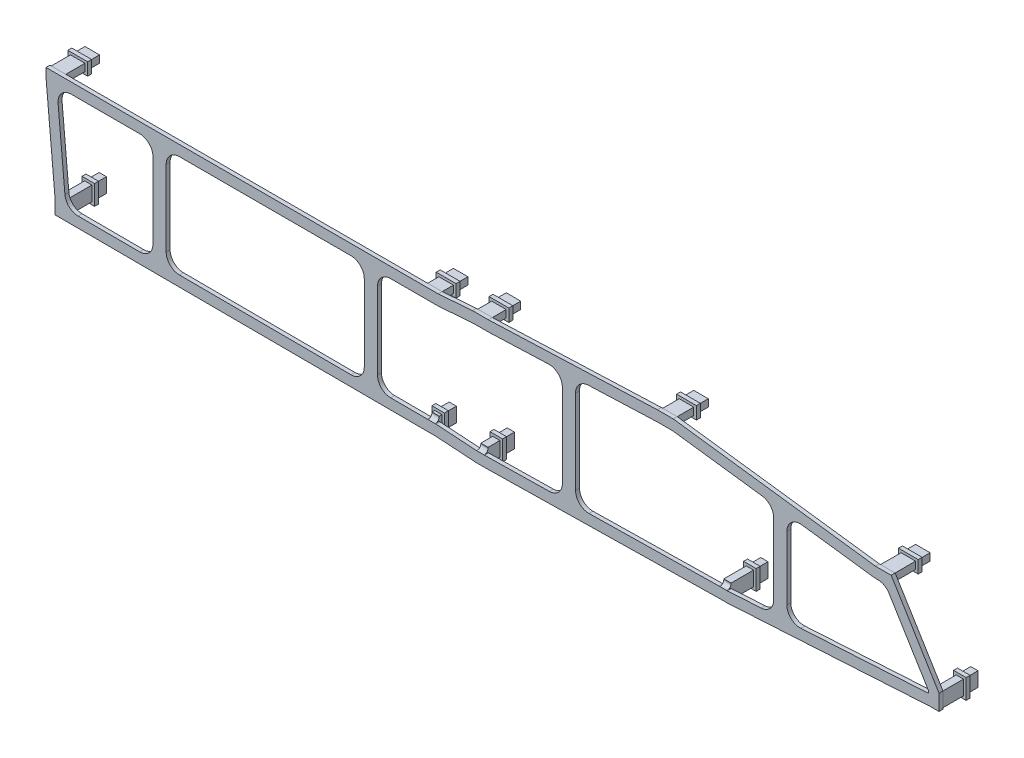
SolidWorks part; units mm, degrees
ref_plane "Front Plane" through (0, 0, 0) normal (0, 0, 1) x (1, 0, 0)
ref_plane "Top Plane" through (0, 0, 0) normal (0, 1, 0) x (1, 0, 0)
ref_plane "Right Plane" through (0, 0, 0) normal (1, 0, 0) x (0, 0, -1)
ref_plane "Plane11" through (0, 0, 7) normal (0, 0, 1) x (1, 0, 0)
ref_plane "Plane12" through (0, 0, 12) normal (0, 0, 1) x (1, 0, 0)
sketch "Sketch13" plane through (0, 0, 12) normal (0, 0, 1) x (1, 0, 0)
  line L0 (-277.75, -90) -> (-284.25, -90)
  line L1 (-284.25, -90) -> (-284.25, -78)
  line L2 (-284.25, -78) -> (-291, -3.25)
  line L3 (-291, -3.25) -> (-291, 3.25)
  line L4 (-291, 3.25) -> (-279, 3.25)
  line L5 (-279, 3.25) -> (-6, 3.25)
  line L6 (-6, 3.25) -> (6, 3.25)
  line L7 (6, 3.25) -> (32, 5.25)
  line L8 (32, 5.25) -> (44, 5.25)
  line L9 (44, 5.25) -> (172, 10.25)
  line L10 (172, 10.25) -> (184, 10.25)
  line L11 (184, 10.25) -> (337, -9.75)
  line L12 (337, -9.75) -> (349, -9.75)
  line L13 (349, -9.75) -> (385.25, -69)
  line L14 (385.25, -69) -> (385.25, -81)
  line L15 (385.25, -81) -> (378.75, -81)
  line L16 (378.75, -81) -> (225.25, -90)
  line L17 (225.25, -90) -> (218.75, -90)
  line L18 (218.75, -90) -> (41.25, -93)
  line L19 (41.25, -93) -> (34.75, -93)
  line L20 (34.75, -93) -> (4.25, -91)
  line L21 (4.25, -91) -> (-2.25, -91)
  line L22 (-2.25, -91) -> (-277.75, -90)
extrude "STUD LINK" add sketch "Sketch13" along normal blind 3
ref_plane "Plane1" through (0, 0, 0) normal (0, 0, 1) x (1, 0, 0)
ref_plane "Plane2" through (0, 0, -2) normal (0, 0, 1) x (1, 0, 0)
ref_plane "Plane3" through (0, 0, -4) normal (0, 0, 1) x (1, 0, 0)
ref_plane "Plane4" through (0, 0, 7) normal (0, 0, 1) x (1, 0, 0)
ref_plane "Plane5" through (0, 0, 0) normal (0, 0, 1) x (1, 0, 0)
ref_plane "Plane6" through (0, 0, -8) normal (0, 0, 1) x (1, 0, 0)
ref_plane "Plane7" through (0, 0, -7) normal (0, 0, 1) x (1, 0, 0)
ref_plane "Plane8" through (0, 0, -7) normal (0, 0, 1) x (1, 0, 0)
ref_plane "Plane9" through (0, 0, -6) normal (0, 0, 1) x (1, 0, 0)
ref_plane "Plane10" through (0, 0, -10) normal (0, 0, 1) x (1, 0, 0)
sketch "Sketch1" plane through (0, 0, 0) normal (0, 0, 1) x (1, 0, 0)
  line L8 (-5.5, 2.75) -> (-5.5, -2.75)
  line L9 (-5.5, -2.75) -> (5.5, -2.75)
  line L10 (5.5, -2.75) -> (5.5, 2.75)
  line L11 (5.5, 2.75) -> (-5.5, 2.75)
  line L12 (-5.5, 2.75) -> (-5.5, -2.75)
  line L13 (-5.5, -2.75) -> (5.5, -2.75)
  line L14 (5.5, -2.75) -> (5.5, 2.75)
  line L15 (5.5, 2.75) -> (-5.5, 2.75)
  dimension "D1" = 0.5
extrude "Boss-Extrude1" add sketch "Sketch1" against normal blind 8 and the other way up to next
sketch "Sketch2" plane through (0, 0, -2) normal (0, 0, 1) x (1, 0, 0)
  line L8 (43.5, 4.75) -> (32.5, 4.75)
  line L9 (43.5, -0.75) -> (43.5, 4.75)
  line L10 (32.5, -0.75) -> (43.5, -0.75)
  line L11 (32.5, 4.75) -> (32.5, -0.75)
  line L12 (43.5, 4.75) -> (32.5, 4.75)
  line L13 (43.5, -0.75) -> (43.5, 4.75)
  line L14 (32.5, -0.75) -> (43.5, -0.75)
  line L15 (32.5, 4.75) -> (32.5, -0.75)
  dimension "D1" = 0.5
extrude "Boss-Extrude2" add sketch "Sketch2" against normal blind 8 and the other way up to next separate body
sketch "Sketch3" plane through (0, 0, -4) normal (0, 0, 1) x (1, 0, 0)
  line L8 (183.5, 9.75) -> (172.5, 9.75)
  line L9 (183.5, 4.25) -> (183.5, 9.75)
  line L10 (172.5, 4.25) -> (183.5, 4.25)
  line L11 (172.5, 9.75) -> (172.5, 4.25)
  line L12 (183.5, 9.75) -> (172.5, 9.75)
  line L13 (183.5, 4.25) -> (183.5, 9.75)
  line L14 (172.5, 4.25) -> (183.5, 4.25)
  line L15 (172.5, 9.75) -> (172.5, 4.25)
  dimension "D1" = 0.5
extrude "Boss-Extrude3" add sketch "Sketch3" against normal blind 8 and the other way up to next separate body
sketch "Sketch4" plane through (0, 0, 7) normal (0, 0, 1) x (1, 0, 0)
  line L8 (3.75, -79.5) -> (-1.75, -79.5)
  line L9 (3.75, -90.5) -> (3.75, -79.5)
  line L10 (-1.75, -90.5) -> (3.75, -90.5)
  line L11 (-1.75, -79.5) -> (-1.75, -90.5)
  line L12 (3.75, -79.5) -> (-1.75, -79.5)
  line L13 (3.75, -90.5) -> (3.75, -79.5)
  line L14 (-1.75, -90.5) -> (3.75, -90.5)
  line L15 (-1.75, -79.5) -> (-1.75, -90.5)
  dimension "D1" = 0.5
extrude "Boss-Extrude4" add sketch "Sketch4" against normal blind 8 and the other way up to next separate body
sketch "Sketch5" plane through (0, 0, 0) normal (0, 0, 1) x (1, 0, 0)
  line L8 (40.75, -81.5) -> (35.25, -81.5)
  line L9 (40.75, -92.5) -> (40.75, -81.5)
  line L10 (35.25, -92.5) -> (40.75, -92.5)
  line L11 (35.25, -81.5) -> (35.25, -92.5)
  line L12 (40.75, -81.5) -> (35.25, -81.5)
  line L13 (40.75, -92.5) -> (40.75, -81.5)
  line L14 (35.25, -92.5) -> (40.75, -92.5)
  line L15 (35.25, -81.5) -> (35.25, -92.5)
  dimension "D1" = 0.5
extrude "Boss-Extrude5" add sketch "Sketch5" against normal blind 8 and the other way up to next separate body
sketch "Sketch6" plane through (0, 0, -8) normal (0, 0, 1) x (1, 0, 0)
  line L8 (224.75, -78.5) -> (219.25, -78.5)
  line L9 (219.25, -78.5) -> (219.25, -89.5)
  line L10 (219.25, -89.5) -> (224.75, -89.5)
  line L11 (224.75, -89.5) -> (224.75, -78.5)
  line L12 (224.75, -78.5) -> (219.25, -78.5)
  line L13 (219.25, -78.5) -> (219.25, -89.5)
  line L14 (219.25, -89.5) -> (224.75, -89.5)
  line L15 (224.75, -89.5) -> (224.75, -78.5)
  dimension "D1" = 0.5
extrude "Boss-Extrude6" add sketch "Sketch6" against normal blind 8 and the other way up to next separate body
sketch "Sketch7" plane through (0, 0, -7) normal (0, 0, 1) x (1, 0, 0)
  line L8 (348.5, -10.25) -> (337.5, -10.25)
  line L9 (348.5, -15.75) -> (348.5, -10.25)
  line L10 (337.5, -15.75) -> (348.5, -15.75)
  line L11 (337.5, -10.25) -> (337.5, -15.75)
  line L12 (348.5, -10.25) -> (337.5, -10.25)
  line L13 (348.5, -15.75) -> (348.5, -10.25)
  line L14 (337.5, -15.75) -> (348.5, -15.75)
  line L15 (337.5, -10.25) -> (337.5, -15.75)
  dimension "D1" = 0.5
extrude "Boss-Extrude7" add sketch "Sketch7" against normal blind 8 and the other way up to next separate body
sketch "Sketch8" plane through (0, 0, -7) normal (0, 0, 1) x (1, 0, 0)
  line L8 (384.75, -69.5) -> (379.25, -69.5)
  line L9 (384.75, -80.5) -> (384.75, -69.5)
  line L10 (379.25, -80.5) -> (384.75, -80.5)
  line L11 (379.25, -69.5) -> (379.25, -80.5)
  line L12 (384.75, -69.5) -> (379.25, -69.5)
  line L13 (384.75, -80.5) -> (384.75, -69.5)
  line L14 (379.25, -80.5) -> (384.75, -80.5)
  line L15 (379.25, -69.5) -> (379.25, -80.5)
  dimension "D1" = 0.5
extrude "Boss-Extrude8" add sketch "Sketch8" against normal blind 8 and the other way up to next separate body
sketch "Sketch9" plane through (0, 0, -6) normal (0, 0, 1) x (1, 0, 0)
  line L8 (-279.5, 2.75) -> (-290.5, 2.75)
  line L9 (-279.5, -2.75) -> (-279.5, 2.75)
  line L10 (-290.5, -2.75) -> (-279.5, -2.75)
  line L11 (-290.5, 2.75) -> (-290.5, -2.75)
  line L12 (-279.5, 2.75) -> (-290.5, 2.75)
  line L13 (-279.5, -2.75) -> (-279.5, 2.75)
  line L14 (-290.5, -2.75) -> (-279.5, -2.75)
  line L15 (-290.5, 2.75) -> (-290.5, -2.75)
  dimension "D1" = 0.5
extrude "Boss-Extrude9" add sketch "Sketch9" against normal blind 8 and the other way up to next separate body
sketch "Sketch10" plane through (0, 0, -10) normal (0, 0, 1) x (1, 0, 0)
  line L8 (-278.25, -78.5) -> (-283.75, -78.5)
  line L9 (-278.25, -89.5) -> (-278.25, -78.5)
  line L10 (-283.75, -89.5) -> (-278.25, -89.5)
  line L11 (-283.75, -78.5) -> (-283.75, -89.5)
  line L12 (-278.25, -78.5) -> (-283.75, -78.5)
  line L13 (-278.25, -89.5) -> (-278.25, -78.5)
  line L14 (-283.75, -89.5) -> (-278.25, -89.5)
  line L15 (-283.75, -78.5) -> (-283.75, -89.5)
  dimension "D1" = 0.5
extrude "Boss-Extrude10" add sketch "Sketch10" against normal blind 8 and the other way up to next (22 mm away) separate body
sketch "Sketch14" plane through (0, 0, 0) normal (0, 0, 1) x (1, 0, 0)
  line L8 (-7.5, -4.75) -> (7.5, -4.75)
  line L9 (7.5, -4.75) -> (7.5, 4.75)
  line L10 (7.5, 4.75) -> (-7.5, 4.75)
  line L11 (-7.5, 4.75) -> (-7.5, -4.75)
  line L12 (-7.5, -4.75) -> (7.5, -4.75)
  line L13 (7.5, -4.75) -> (7.5, 4.75)
  line L14 (7.5, 4.75) -> (-7.5, 4.75)
  line L15 (-7.5, 4.75) -> (-7.5, -4.75)
  dimension "D1" = 1.5
extrude "Boss-Extrude14" add sketch "Sketch14" along normal blind 3
sketch "Sketch15" plane through (0, 0, -2) normal (0, 0, 1) x (1, 0, 0)
  line L8 (45.5, 6.75) -> (30.5, 6.75)
  line L9 (30.5, 6.75) -> (30.5, -2.75)
  line L10 (30.5, -2.75) -> (45.5, -2.75)
  line L11 (45.5, -2.75) -> (45.5, 6.75)
  line L12 (45.5, 6.75) -> (30.5, 6.75)
  line L13 (30.5, 6.75) -> (30.5, -2.75)
  line L14 (30.5, -2.75) -> (45.5, -2.75)
  line L15 (45.5, -2.75) -> (45.5, 6.75)
  dimension "D1" = 1.5
extrude "Boss-Extrude15" add sketch "Sketch15" along normal blind 3
sketch "Sketch16" plane through (0, 0, -4) normal (0, 0, 1) x (1, 0, 0)
  line L8 (185.5, 11.75) -> (170.5, 11.75)
  line L9 (170.5, 11.75) -> (170.5, 2.25)
  line L10 (170.5, 2.25) -> (185.5, 2.25)
  line L11 (185.5, 2.25) -> (185.5, 11.75)
  line L12 (185.5, 11.75) -> (170.5, 11.75)
  line L13 (170.5, 11.75) -> (170.5, 2.25)
  line L14 (170.5, 2.25) -> (185.5, 2.25)
  line L15 (185.5, 2.25) -> (185.5, 11.75)
  dimension "D1" = 1.5
extrude "Boss-Extrude16" add sketch "Sketch16" along normal blind 3
sketch "Sketch17" plane through (0, 0, 7) normal (0, 0, 1) x (1, 0, 0)
  line L8 (5.75, -77.5) -> (-3.75, -77.5)
  line L9 (-3.75, -77.5) -> (-3.75, -92.5)
  line L10 (-3.75, -92.5) -> (5.75, -92.5)
  line L11 (5.75, -92.5) -> (5.75, -77.5)
  line L12 (5.75, -77.5) -> (-3.75, -77.5)
  line L13 (-3.75, -77.5) -> (-3.75, -92.5)
  line L14 (-3.75, -92.5) -> (5.75, -92.5)
  line L15 (5.75, -92.5) -> (5.75, -77.5)
  dimension "D1" = 1.5
extrude "Boss-Extrude17" add sketch "Sketch17" along normal blind 3
sketch "Sketch18" plane through (0, 0, 0) normal (0, 0, 1) x (1, 0, 0)
  line L8 (42.75, -79.5) -> (33.25, -79.5)
  line L9 (42.75, -94.5) -> (42.75, -79.5)
  line L10 (33.25, -94.5) -> (42.75, -94.5)
  line L11 (33.25, -79.5) -> (33.25, -94.5)
  line L12 (42.75, -79.5) -> (33.25, -79.5)
  line L13 (42.75, -94.5) -> (42.75, -79.5)
  line L14 (33.25, -94.5) -> (42.75, -94.5)
  line L15 (33.25, -79.5) -> (33.25, -94.5)
  dimension "D1" = 1.5
extrude "Boss-Extrude18" add sketch "Sketch18" along normal blind 3
sketch "Sketch19" plane through (0, 0, -8) normal (0, 0, 1) x (1, 0, 0)
  line L8 (226.75, -76.5) -> (217.25, -76.5)
  line L9 (226.75, -91.5) -> (226.75, -76.5)
  line L10 (217.25, -91.5) -> (226.75, -91.5)
  line L11 (217.25, -76.5) -> (217.25, -91.5)
  line L12 (226.75, -76.5) -> (217.25, -76.5)
  line L13 (226.75, -91.5) -> (226.75, -76.5)
  line L14 (217.25, -91.5) -> (226.75, -91.5)
  line L15 (217.25, -76.5) -> (217.25, -91.5)
  dimension "D1" = 1.5
extrude "Boss-Extrude19" add sketch "Sketch19" along normal blind 3
sketch "Sketch20" plane through (0, 0, -7) normal (0, 0, 1) x (1, 0, 0)
  line L8 (350.5, -8.25) -> (335.5, -8.25)
  line L9 (335.5, -8.25) -> (335.5, -17.75)
  line L10 (335.5, -17.75) -> (350.5, -17.75)
  line L11 (350.5, -17.75) -> (350.5, -8.25)
  line L12 (350.5, -8.25) -> (335.5, -8.25)
  line L13 (335.5, -8.25) -> (335.5, -17.75)
  line L14 (335.5, -17.75) -> (350.5, -17.75)
  line L15 (350.5, -17.75) -> (350.5, -8.25)
  dimension "D1" = 1.5
extrude "Boss-Extrude20" add sketch "Sketch20" along normal blind 3
sketch "Sketch21" plane through (0, 0, -7) normal (0, 0, 1) x (1, 0, 0)
  line L8 (386.75, -67.5) -> (377.25, -67.5)
  line L9 (386.75, -82.5) -> (386.75, -67.5)
  line L10 (377.25, -82.5) -> (386.75, -82.5)
  line L11 (377.25, -67.5) -> (377.25, -82.5)
  line L12 (386.75, -67.5) -> (377.25, -67.5)
  line L13 (386.75, -82.5) -> (386.75, -67.5)
  line L14 (377.25, -82.5) -> (386.75, -82.5)
  line L15 (377.25, -67.5) -> (377.25, -82.5)
  dimension "D1" = 1.5
extrude "Boss-Extrude21" add sketch "Sketch21" along normal blind 3
sketch "Sketch22" plane through (0, 0, -6) normal (0, 0, 1) x (1, 0, 0)
  line L8 (-277.5, 4.75) -> (-292.5, 4.75)
  line L9 (-277.5, -4.75) -> (-277.5, 4.75)
  line L10 (-292.5, -4.75) -> (-277.5, -4.75)
  line L11 (-292.5, 4.75) -> (-292.5, -4.75)
  line L12 (-277.5, 4.75) -> (-292.5, 4.75)
  line L13 (-277.5, -4.75) -> (-277.5, 4.75)
  line L14 (-292.5, -4.75) -> (-277.5, -4.75)
  line L15 (-292.5, 4.75) -> (-292.5, -4.75)
  dimension "D1" = 1.5
extrude "Boss-Extrude22" add sketch "Sketch22" along normal blind 3
sketch "Sketch23" plane through (0, 0, -10) normal (0, 0, 1) x (1, 0, 0)
  line L15 (-276.25, -76.5) -> (-285.75, -76.5)
  line L16 (-285.75, -76.5) -> (-285.75, -91.5)
  line L17 (-276.25, -91.5) -> (-276.25, -76.5)
  line L18 (-285.75, -91.5) -> (-276.25, -91.5)
  line L19 (-276.25, -76.5) -> (-285.75, -76.5)
  line L20 (-285.75, -76.5) -> (-285.75, -91.5)
  line L21 (-276.25, -91.5) -> (-276.25, -76.5)
  line L22 (-285.75, -91.5) -> (-276.25, -91.5)
  dimension "D1" = 1.5
extrude "Boss-Extrude23" add sketch "Sketch23" along normal blind 3
sketch "Sketch24" plane through (0, 0, 15) normal (0, 0, 1) x (1, 0, 0)
  line L42 (-276.25, -82.0054) -> (-2.2355, -83)
  line L43 (-2.2355, -83) -> (4.512, -83)
  line L44 (4.512, -83) -> (35.012, -85)
  line L45 (35.012, -85) -> (41.1824, -85)
  line L46 (41.1824, -85) -> (218.6824, -82)
  line L47 (218.6824, -82) -> (225.0157, -82)
  line L48 (225.0157, -82) -> (377.25, -73.0742)
  line L49 (377.25, -73.0742) -> (377.25, -71.2531)
  line L50 (377.25, -71.2531) -> (344.516, -17.75)
  line L51 (344.516, -17.75) -> (336.4793, -17.75)
  line L52 (336.4793, -17.75) -> (183.4793, 2.25)
  line L53 (183.4793, 2.25) -> (172.1562, 2.25)
  line L54 (172.1562, 2.25) -> (44.1562, -2.75)
  line L55 (44.1562, -2.75) -> (32.3072, -2.75)
  line L56 (32.3072, -2.75) -> (6.3072, -4.75)
  line L57 (6.3072, -4.75) -> (-282.832, -4.75)
  line L58 (-282.832, -4.75) -> (-276.25, -77.6395)
  line L59 (-276.25, -77.6395) -> (-276.25, -82.0054)
  line L60 (-276.25, -82.0054) -> (-2.2355, -83)
  line L61 (-2.2355, -83) -> (4.512, -83)
  line L62 (4.512, -83) -> (35.012, -85)
  line L63 (35.012, -85) -> (41.1824, -85)
  line L64 (41.1824, -85) -> (218.6824, -82)
  line L65 (218.6824, -82) -> (225.0157, -82)
  line L66 (225.0157, -82) -> (377.25, -73.0742)
  line L67 (377.25, -73.0742) -> (377.25, -71.2531)
  line L68 (377.25, -71.2531) -> (344.516, -17.75)
  line L69 (344.516, -17.75) -> (336.4793, -17.75)
  line L70 (336.4793, -17.75) -> (183.4793, 2.25)
  line L71 (183.4793, 2.25) -> (172.1562, 2.25)
  line L72 (172.1562, 2.25) -> (44.1562, -2.75)
  line L73 (44.1562, -2.75) -> (32.3072, -2.75)
  line L74 (32.3072, -2.75) -> (6.3072, -4.75)
  line L75 (6.3072, -4.75) -> (-282.832, -4.75)
  line L76 (-282.832, -4.75) -> (-276.25, -77.6395)
  line L77 (-276.25, -77.6395) -> (-276.25, -82.0054)
  dimension "D1" = 8
extrude "Cut-Extrude1" cut sketch "Sketch24" against normal blind 3
ref_plane "Plane13" through (0, -50, 0) normal (0, 1, 0) x (1, 0, 0)
sketch "Sketch25" plane through (0, -50, 0) normal (0, 1, 0) x (1, 0, 0)
  line L0 (6, -12) -> (-291, -12) construction
  line L1 (-210, -12) -> (-200, -12)
  line L2 (-210, -12) -> (-210, -15)
  line L3 (-210, -15) -> (-200, -15)
  line L4 (-200, -12) -> (-200, -15)
  line L5 (6, -15) -> (-291, -15) construction
  line L6 (172, -12) -> (44, -12) construction
  line L7 (-50, -12) -> (-40, -12)
  line L8 (-50, -12) -> (-50, -15)
  line L9 (-50, -15) -> (-40, -15)
  line L10 (-40, -12) -> (-40, -15)
  line L11 (100, -12) -> (110, -12)
  line L12 (100, -12) -> (100, -15)
  line L13 (100, -15) -> (110, -15)
  line L14 (110, -12) -> (110, -15)
  line L15 (172, -15) -> (44, -15) construction
  line L16 (337, -12) -> (184, -12) construction
  line L17 (260, -12) -> (270, -12)
  line L18 (260, -12) -> (260, -15)
  line L19 (260, -15) -> (270, -15)
  line L20 (270, -12) -> (270, -15)
  line L21 (337, -15) -> (184, -15) construction
  dimension "D1" = 10
  dimension "D2" = 150
  dimension "D3" = 40
  dimension "D4" = 100
  dimension "D5" = 150
extrude "Boss-Extrude24" add sketch "Sketch25" along normal up to next and the other way up to next
fillet "Fillet1" radius 3 3 edges at (222, -82, 12) (1, -83, 12) (38, -85, 12)
fillet "Fillet2" radius 10 20 edges at (-210, -82.2459, 13.5) (-210, -4.75, 13.5) (-282.832, -4.75, 13.5) (-276.25, -82.0054, 13.5) (100, -84.0059, 13.5) (100, -0.5686, 13.5) (-50, -4.75, 13.5) (-50, -82.8266, 13.5) (-40, -82.8629, 13.5) (-200, -82.2822, 13.5) (-200, -4.75, 13.5) (-40, -4.75, 13.5) (110, -0.178, 13.5) (110, -83.8369, 13.5) (270, -79.3625, 13.5) (260, -79.9488, 13.5) (260, -7.7527, 13.5) (270, -9.0599, 13.5) (336.4793, -17.75, 13.5) (344.516, -17.75, 13.5)
ref_plane "Plane14" through (19.5, 0, 0) normal (-1, 0, 0) x (0, 0, 1)
sketch "Sketch26" plane through (19.5, 0, 0) normal (-1, 0, 0) x (0, 0, 1)
  line L1 (-177.7155, 99.6631) -> (210.2216, 99.6631)
  line L2 (-177.7155, 99.6631) -> (-177.7155, -244.2201)
  line L3 (-177.7155, -244.2201) -> (210.2216, -244.2201)
  line L4 (210.2216, 99.6631) -> (210.2216, -244.2201)
extrude "Cut-Extrude2" [suppressed] cut sketch "Sketch26" along normal through all
